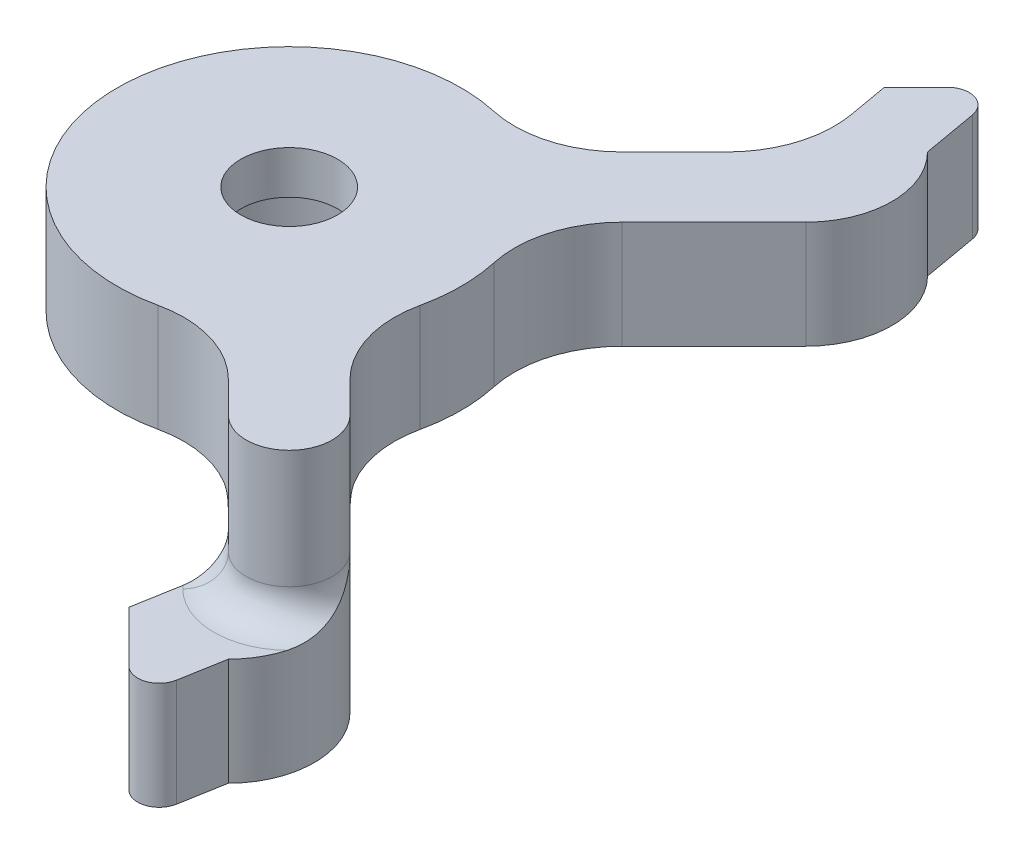
SolidWorks part; units mm, degrees
ref_plane "Plan de face" through (0, 0, 0) normal (0, 0, 1) x (1, 0, 0)
ref_plane "Plan de dessus" through (0, 0, 0) normal (0, 1, 0) x (1, 0, 0)
ref_plane "Plan de droite" through (0, 0, 0) normal (1, 0, 0) x (0, 0, -1)
sketch "Esquisse1" plane through (0, 0, 0) normal (0, 1, 0) x (1, 0, 0)
  circle A0 centre (0, 0) radius 8
  circle A2 centre (0, 0) radius 2.25
  dimension "D1" = 4.5
  dimension "D2" = 16
extrude "Boss.-Extru.1" add sketch "Esquisse1" along normal blind 5
sketch "Esquisse2" plane through (0, 0, 0) normal (0, -1, 0) x (1, 0, 0)
  circle A0 centre (0, 0) radius 4.75
  dimension "D1" = 9.5
extrude "Enlèv. mat.-Extru.1" cut sketch "Esquisse2" against normal blind 3
sketch "Esquisse3" plane through (0, 0, 0) normal (0, 1, 0) x (1, 0, 0)
  line L0 (0, 0) -> (17.955, 0) construction
  line L1 (0, 0) -> (9.1924, -9.1924) construction
  line L2 (4.063, -6.8914) -> (7.7782, -10.6066)
  line L3 (4.063, -6.8914) -> (6.8914, -4.063)
  line L5 (6.8914, -4.063) -> (10.6066, -7.7782)
  line L6 (4.063, -6.8914) -> (10.6066, -7.7782) construction
  line L7 (7.7782, -10.6066) -> (6.8914, -4.063) construction
  line L8 (7.7782, -10.6066) -> (10.6066, -7.7782) construction
  line L9 (10.6066, -13.435) -> (7.7782, -10.6066)
  arc A0 (10.6066, -7.7782) -> (10.6066, -13.435) centre (7.7782, -10.6066) cw
  circle A2 centre (0, 0) radius 8 construction
  point P5 (7.3348, -7.3348)
  dimension "D1" = 45
  dimension "D2" = 4
  dimension "D3" = 13
extrude "Boss.-Extru.3" add sketch "Esquisse3" along normal up to surface (5 mm away) up to face at (0, 5, 8)
sketch "Esquisse4" plane through (0, 0, 0) normal (0, 1, 0) x (-1, 0, 0)
  line L1 (-7.7782, 10.6066) -> (-10.6066, 13.435)
  line L2 (-10.6066, 7.7782) -> (-9.7227, 6.8943)
  line L3 (-9.7227, 6.8943) -> (-6.8943, 9.7227)
  line L4 (-4.063, 6.8914) -> (-10.6066, 13.435) construction
  line L5 (-6.8943, 9.7227) -> (-7.7782, 10.6066)
  arc A0 (-10.6066, 13.435) -> (-10.6066, 7.7782) centre (-7.7782, 10.6066) ccw construction
  arc A1 (-10.6066, 13.435) -> (-10.6066, 7.7782) centre (-7.7782, 10.6066) ccw
  dimension "D1" = 1.25
extrude "Boss.-Extru.4" add sketch "Esquisse4" against normal blind 7
sketch "Esquisse6" plane through (0, -7, 0) normal (0, -1, 0) x (1, 0, 0)
  line L0 (6.8943, 9.7227) -> (6.1997, 13.6619)
  line L1 (6.1997, 13.6619) -> (9.912, 17.3743)
  line L2 (9.912, 17.3743) -> (10.6066, 13.435)
  line L3 (10.6066, 13.435) -> (6.8943, 9.7227)
  line L4 (4.063, 6.8914) -> (6.8943, 9.7227) construction
  line L5 (6.8943, 9.7227) -> (10.6066, 13.435) construction
  dimension "D1" = 4
  dimension "D2" = 125
  dimension "D3" = 0
extrude "Boss.-Extru.6" add sketch "Esquisse6" against normal blind 5
fillet "Congé5" radius 2 1 edges at (10.6066, 1.5, 13.435)
fillet "Congé1" radius 2 1 edges at (8.3085, 0, 8.3085)
sketch "Esquisse5" plane through (0, 5, 0) normal (0, 1, 0) x (1, 0, 0)
  line L0 (0, 0) -> (12.0208, 12.0208) construction
  line L1 (0, 0) -> (18.7104, 0) construction
  line L2 (6.8914, 4.063) -> (13.435, 10.6066)
  line L3 (6.8914, 4.063) -> (4.063, 6.8914)
  line L4 (13.435, 10.6066) -> (10.6066, 13.435) construction
  line L5 (4.063, 6.8914) -> (10.6066, 13.435)
  line L6 (6.8914, 4.063) -> (10.6066, 13.435) construction
  line L7 (13.435, 10.6066) -> (4.063, 6.8914) construction
  line L8 (13.435, 16.2635) -> (10.6066, 13.435) construction
  line L9 (10.6066, 13.435) -> (9.8252, 17.8667)
  line L10 (9.8252, 17.8667) -> (12.6536, 20.6951)
  line L11 (12.6536, 20.6951) -> (13.435, 16.2635)
  arc A1 (13.435, 10.6066) -> (13.435, 16.2635) centre (10.6066, 13.435) ccw
  arc A2 (6.8914, -4.063) -> (4.063, -6.8914) centre (0, 0) ccw construction
  point P5 (8.749, 8.749)
  dimension "D1" = 45
  dimension "D2" = 4
  dimension "D3" = 17
  dimension "D4" = 125
  dimension "D5" = 4.5
extrude "Boss.-Extru.5" add sketch "Esquisse5" against normal up to surface (5 mm away) up to face at (3.4022, 0, 3.4022)
fillet "Congé2" radius 5 5 edges at (4.063, 2.5, 6.8914) (6.8914, 2.5, -4.063) (6.8914, 2.5, 4.063) (10.6066, 2.5, -13.435) (4.063, 2.5, -6.8914)
fillet "Congé3" radius 1.5 2 edges at (7.3362, -2, 10.1647) (10.6066, -2, 10.6066)
fillet "Congé4" radius 1 2 edges at (12.6536, 2.5, -20.6951) (9.912, -4.5, 17.3743)
